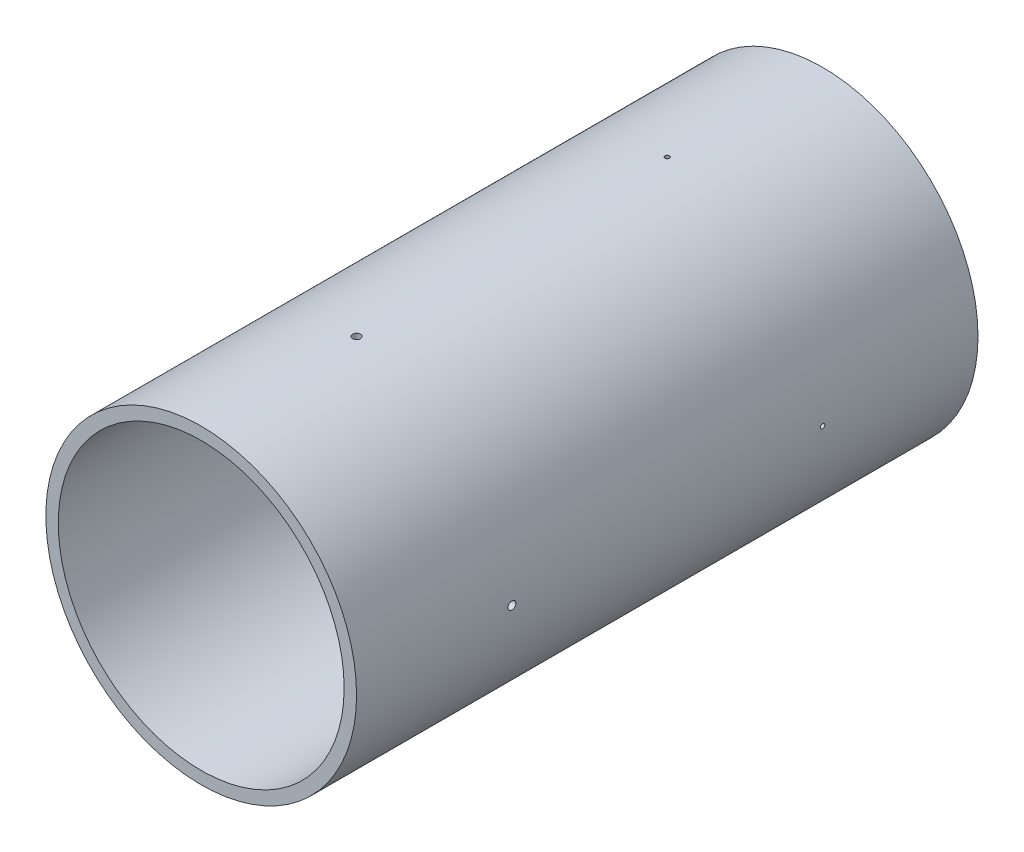
SolidWorks part; units mm, degrees
ref_plane "Front Plane" through (0, 0, 0) normal (0, 0, 1) x (1, 0, 0)
ref_plane "Top Plane" through (0, 0, 0) normal (0, 1, 0) x (1, 0, 0)
ref_plane "Right Plane" through (0, 0, 0) normal (1, 0, 0) x (0, 0, -1)
sketch "Sketch1" plane through (0, 0, 0) normal (0, 0, 1) x (1, 0, 0)
  circle A0 centre (0, 0) radius 79.375
  circle A1 centre (0, 0) radius 73.025
  dimension "D1" = 158.75
  dimension "D2" = 6.35
extrude "Boss-Extrude1" add sketch "Sketch1" along normal blind 317.5
ref_plane "Plane1" through (0, 79.375, 0) normal (0, 1, 0) x (1, 0, 0)
sketch "Sketch2" plane through (0, 79.375, 0) normal (0, 1, 0) x (1, 0, 0)
  line L0 (79.375, 0) -> (-79.375, 0) construction
  point P0 (0, -79.375)
  dimension "D1" = 79.375
hole_wizard "#4-40 Tapped Hole1" positions "Sketch5" profile "Sketch6" tap size "#4-40" standard "ANSI Inch" end condition up to next
sketch "Sketch5" plane through (0, 79.375, 0) normal (0, 1, 0) x (1, 0, 0)
  point P0 (0, -79.375)
sketch "Sketch6" plane through (0, 79.375, 79.375) normal (1, 0, 0) x (0, 0, 1)
  line L0 (0, 0) -> (0, 6.35)
  line L1 (0, 6.35) -> (1.1303, 6.35)
  line L2 (1.1303, 6.35) -> (1.1303, 0)
  line L5 (1.1303, 0) -> (0, 0)
  line L11 (0, -6.35) -> (0, 107.95) construction
  dimension "Thru Tap Drill Dia." = 2.2606
  dimension "Thru Tap Drill Depth" = 6.35
cosmetic thread "Hole Thread1"
sketch "Sketch7" plane through (0, 79.375, 0) normal (0, 1, 0) x (1, 0, 0)
  line L0 (-79.375, -317.5) -> (79.375, -317.5) construction
  point P0 (0, -238.125)
  dimension "D1" = 79.375
hole_wizard "#10-32 Tapped Hole1" positions "Sketch8" profile "Sketch9" tap size "#10-32" standard "ANSI Inch" end condition up to next
sketch "Sketch8" plane through (0, 79.375, 0) normal (0, 1, 0) x (1, 0, 0)
  point P0 (0, -238.125)
sketch "Sketch9" plane through (0, 79.375, 238.125) normal (1, 0, 0) x (0, 0, 1)
  line L0 (0, 0) -> (0, 6.35)
  line L1 (0, 6.35) -> (2.0193, 6.35)
  line L2 (2.0193, 6.35) -> (2.0193, 0)
  line L5 (2.0193, 0) -> (0, 0)
  line L11 (0, -6.35) -> (0, 107.95) construction
  dimension "Thru Tap Drill Dia." = 4.0386
  dimension "Thru Tap Drill Depth" = 6.35
cosmetic thread "Hole Thread2"
pattern_circular "CirPattern1" count 4 over 360 about axis through (0, 0, 317.5) along (0, 0, 1) of "#4-40 Tapped Hole1", "#10-32 Tapped Hole1"
cosmetic thread "Hole Thread3"
cosmetic thread "Hole Thread4"
cosmetic thread "Hole Thread5"
cosmetic thread "Hole Thread6"
cosmetic thread "Hole Thread7"
cosmetic thread "Hole Thread8"
